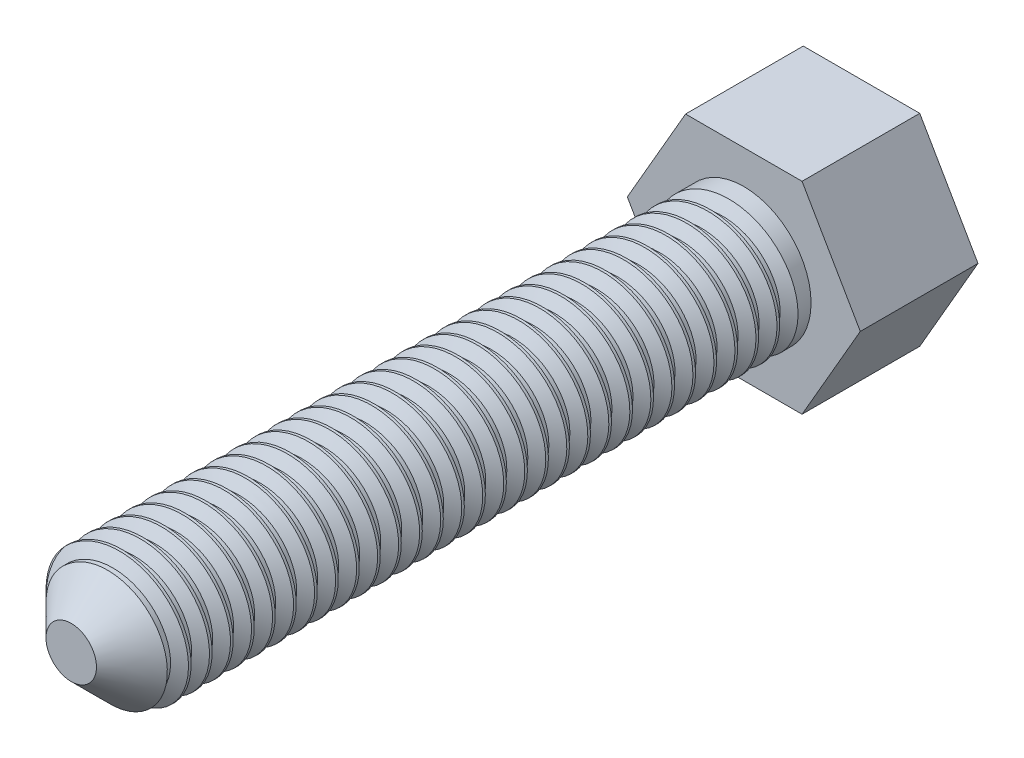
SolidWorks part; units mm, degrees
ref_plane "Спереди" through (0, 0, 0) normal (0, 0, 1) x (1, 0, 0)
ref_plane "Сверху" through (0, 0, 0) normal (0, 1, 0) x (1, 0, 0)
ref_plane "Справа" through (0, 0, 0) normal (1, 0, 0) x (0, 0, -1)
sketch "Эскиз1" plane through (0, 0, 0) normal (0, 0, 1) x (1, 0, 0)
  line L1 (-6.9282, 0) -> (-3.4641, -6)
  line L2 (-3.4641, -6) -> (3.4641, -6)
  line L3 (3.4641, -6) -> (6.9282, 0)
  line L4 (6.9282, 0) -> (3.4641, 6)
  line L5 (3.4641, 6) -> (-3.4641, 6)
  line L6 (-3.4641, 6) -> (-6.9282, 0)
  circle A1 centre (0, 0) radius 6 construction
  dimension "D1" = 12
extrude "Бобышка-Вытянуть1" add sketch "Эскиз1" against normal blind 7
sketch "Эскиз2" plane through (0, 0, 0) normal (0, 0, 1) x (1, 0, 0)
  circle A0 centre (0, 0) radius 4
  dimension "D1" = 8
extrude "Бобышка-Вытянуть2" add sketch "Эскиз2" along normal blind 40
chamfer "Фаска1" distance 2.5 angle 45 1 edges at (4, 0, 40)
thread "Резьба1" pitch 1.25 method cut profile "Профиль резьбы1" start angle 0, offset 2.5, length 38.5, pitch 1.25, diameter 8
ref_plane "Плоскость1" through (-4, 0, 40) normal (0, -1, 0) x (-1, 0, 0)
sketch "Профиль резьбы1" plane through (-4, 0, 40) normal (0, -1, 0) x (-1, 0, 0)
  line L0 (0, 0) -> (0, 1.25) construction
  line L11 (0, 0) -> (0, 1.0937)
  line L12 (0, 1.0937) -> (-0.6766, 0.7031)
  line L13 (-0.6766, 0.7031) -> (-0.6766, 0.3906)
  line L15 (-0.6766, 0.3906) -> (0, 0)
  line L17 (-0.6766, 0.5469) -> (0, 0.5469) construction
  point P2 (0, 0)
  dimension "Pitch" = 1.25
  dimension "Profile_Angle" = 60
  dimension "Profile_Land" = 0.3125
  dimension "Profile_Height" = 0.6766
